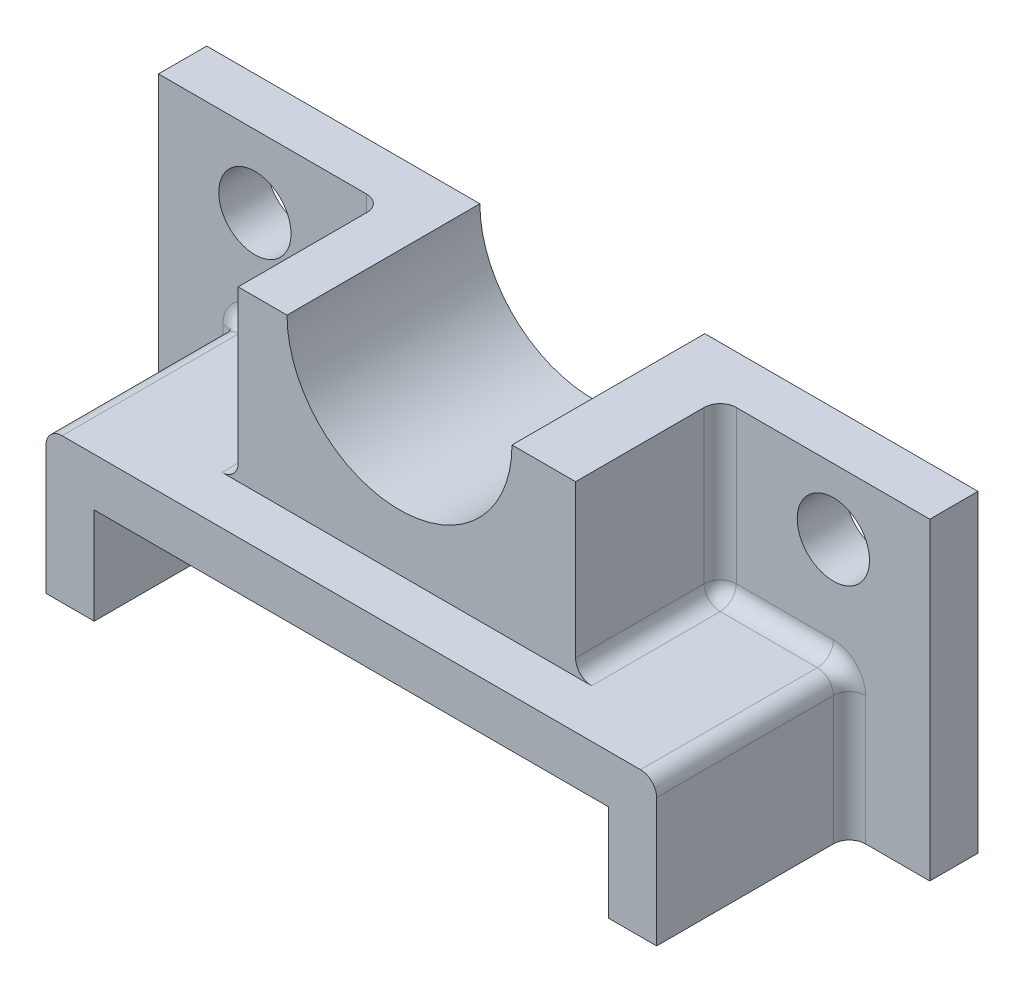
SolidWorks part; units mm, degrees
ref_plane "Front Plane" through (0, 0, 0) normal (0, 0, 1) x (1, 0, 0)
ref_plane "Top Plane" through (0, 0, 0) normal (0, 1, 0) x (1, 0, 0)
ref_plane "Right Plane" through (0, 0, 0) normal (1, 0, 0) x (0, 0, -1)
sketch "Sketch1" plane through (0, 0, 0) normal (0, 0, 1) x (1, 0, 0)
  line L0 (-26.8832, 22.3409) -> (-26.8832, -10.9966)
  line L1 (-71.1942, 22.3409) -> (81.2058, 22.3409)
  line L2 (-71.1942, 22.3409) -> (-71.1942, -39.5716)
  line L3 (-71.1942, -39.5716) -> (81.2058, -39.5716)
  line L4 (81.2058, 22.3409) -> (81.2058, -39.5716)
  line L5 (-26.8832, -10.9966) -> (39.7918, -10.9966)
  line L6 (39.7918, -10.9966) -> (39.7918, 22.3409)
  line L7 (-55.3192, -39.5716) -> (-55.3192, -10.9966)
  line L8 (-55.3192, -10.9966) -> (65.3308, -10.9966)
  line L9 (65.3308, -10.9966) -> (65.3308, -39.5716)
  line L10 (-45.7942, -37.9841) -> (-45.7942, -20.5216)
  line L11 (-45.7942, -20.5216) -> (55.8058, -20.5216)
  line L12 (55.8058, -20.5216) -> (55.8058, -37.9841)
  line L13 (-45.7942, -37.9841) -> (-45.7942, -39.5716)
  line L14 (55.8058, -37.9841) -> (55.8058, -39.5716)
  circle A0 centre (5.0058, 22.3409) radius 22.225
  circle A1 centre (-52.1442, 8.0534) radius 7.1437
  circle A2 centre (62.1558, 9.3512) radius 7.1438
  dimension "D8" = 114.3
  dimension "D9" = 14.2875
  dimension "D10" = 14.2875
  dimension "D11" = 19.05
  dimension "D1" = 152.4
  dimension "D2" = 61.9125
  dimension "D3" = 66.675
  dimension "D4" = 28.575
  dimension "D6" = 15.875
  dimension "D7" = 101.6
  dimension "D5" = 19.05
extrude "Boss-Extrude1" add sketch "Sketch1" along normal blind 9.525 contours L7 L8 L0 L1 L2 L3 A1 | L8 L9 L3 L4 L1 L6 A2 region at (-52.4003, -2.4749, 0) region at (63.8006, -3.0692, 0)
extrude "Boss-Extrude2" add sketch "Sketch1<4>" along normal blind 47.625 contours L12 L14 L3 L9 L8 L5 L7 L13 L10 L11 region at (5.0058, -19.1881, 0)
sketch "Sketch1<4>" plane through (0, 0, 0) normal (0, 0, 1) x (1, 0, 0) same geometry as "Sketch1"
extrude "Boss-Extrude3" add sketch "Sketch1<5>" along normal blind 38.1 contours A0 L1 L0 L5 L6 region at (-22.0512, 21.5954, 0)
sketch "Sketch1<5>" plane through (0, 0, 0) normal (0, 0, 1) x (1, 0, 0) same geometry as "Sketch1"
fillet "Fillet1" radius 3.175 10 edges at (-55.3192, -10.9966, 28.575) (-26.8832, 5.6721, 9.525) (-26.8832, -10.9966, 23.8125) (-55.3192, -25.2841, 9.525) (-41.1012, -10.9966, 9.525) (65.3308, -25.2841, 9.525) (52.5613, -10.9966, 9.525) (39.7918, 5.6721, 9.525) (39.7918, -10.9966, 23.8125) (65.3308, -10.9966, 28.575)
